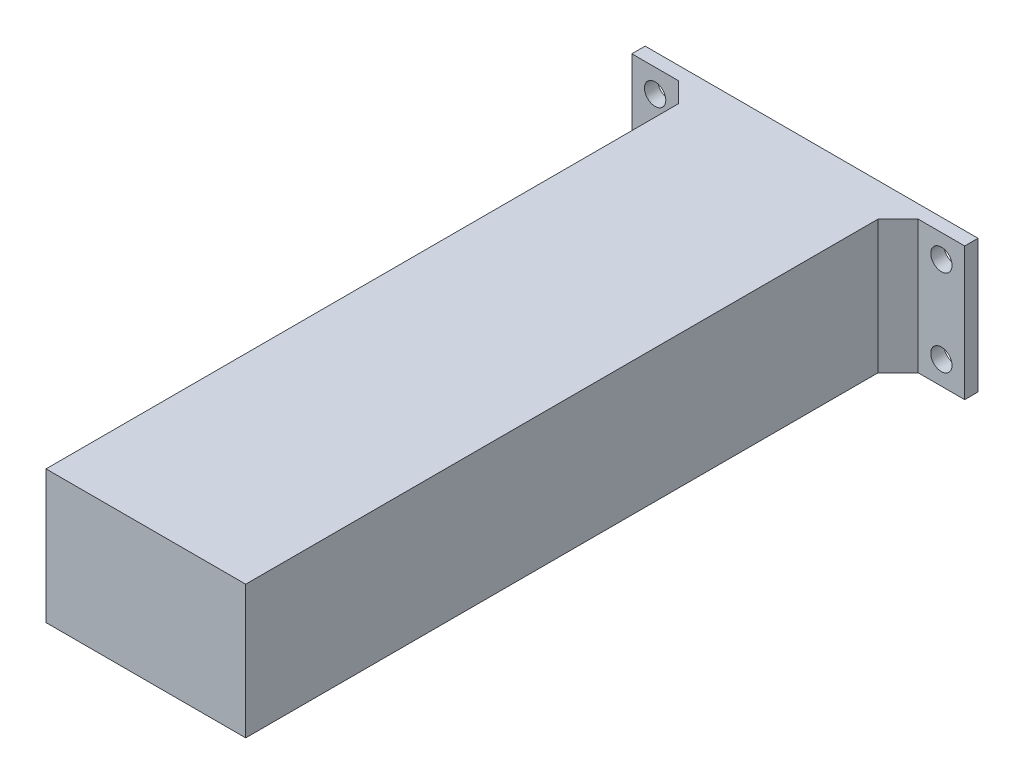
SolidWorks part; units mm, degrees
ref_plane "正面" through (0, 0, 0) normal (0, 0, 1) x (1, 0, 0)
ref_plane "平面" through (0, 0, 0) normal (0, 1, 0) x (1, 0, 0)
ref_plane "右側面" through (0, 0, 0) normal (1, 0, 0) x (0, 0, -1)
sketch "ｽｹｯﾁ1" plane through (0, 0, 0) normal (0, 0, 1) x (1, 0, 0)
  line L1 (-12.7289, 5.1915) -> (17.2711, 5.1915)
  line L2 (-12.7289, 5.1915) -> (-12.7289, -14.8085)
  line L3 (-12.7289, -14.8085) -> (17.2711, -14.8085)
  line L4 (17.2711, 5.1915) -> (17.2711, -14.8085)
  dimension "D1" = 30
  dimension "D2" = 20
extrude "ﾎﾞｽ - 押し出し1" add sketch "ｽｹｯﾁ1" along normal blind 100
sketch "ｽｹｯﾁ3" plane through (17.2711, 0, 0) normal (1, 0, 0) x (0, 0, -1)
  line L0 (-100, -14.8085) -> (0, -14.8085) construction
  line L1 (0, 5.1915) -> (-2, 5.1915)
  line L2 (0, 5.1915) -> (0, -14.8085)
  line L3 (0, -14.8085) -> (-2, -14.8085)
  line L4 (-2, 5.1915) -> (-2, -14.8085)
  dimension "D2" = 2
extrude "ﾎﾞｽ - 押し出し2" add sketch "ｽｹｯﾁ3" along normal blind 10
sketch "ｽｹｯﾁ5" plane through (0, 5.1915, 0) normal (0, 1, 0) x (1, 0, 0)
  line L0 (17.2711, -5) -> (20.2711, -2)
  line L1 (17.2711, -100) -> (17.2711, -2) construction
  line L2 (27.2711, -2) -> (17.2711, -2) construction
  line L3 (20.2711, -2) -> (17.2711, -2)
  line L4 (17.2711, -2) -> (17.2711, -5)
  dimension "D1" = 3
extrude "ﾎﾞｽ - 押し出し3" add sketch "ｽｹｯﾁ5" against normal through all
sketch "ｽｹｯﾁ6" plane through (0, 0, 2) normal (0, 0, 1) x (1, 0, 0)
  line L0 (23.7711, 1.6915) -> (20.2711, 1.6915) construction
  line L1 (20.2711, -14.8085) -> (20.2711, 5.1915) construction
  line L2 (23.7711, 1.6915) -> (27.2711, 1.6915) construction
  line L3 (27.2711, 5.1915) -> (27.2711, -14.8085) construction
  line L4 (23.7711, -11.3085) -> (20.2711, -11.3085) construction
  line L5 (23.7711, -11.3085) -> (27.2711, -11.3085) construction
  line L6 (23.7711, -11.3085) -> (23.7711, -14.8085) construction
  line L7 (27.2711, -14.8085) -> (20.2711, -14.8085) construction
  line L8 (23.7711, 1.6915) -> (23.7711, 5.1915) construction
  line L9 (27.2711, 5.1915) -> (20.2711, 5.1915) construction
  circle A0 centre (23.7711, 1.6915) radius 1.6
  circle A1 centre (23.7711, -11.3085) radius 1.6
  dimension "D1" = 3.2
  dimension "D2" = 3.2
extrude "ｶｯﾄ - 押し出し2" cut sketch "ｽｹｯﾁ6" against normal through all
sketch "ｽｹｯﾁ7" plane through (-12.7289, 0, 0) normal (-1, 0, 0) x (0, 0, 1)
  line L0 (100, 5.1915) -> (0, 5.1915) construction
  line L1 (0, -14.8085) -> (2, -14.8085)
  line L2 (0, -14.8085) -> (0, 5.1915)
  line L3 (0, 5.1915) -> (2, 5.1915)
  line L4 (2, -14.8085) -> (2, 5.1915)
  dimension "D1" = 2
extrude "ﾎﾞｽ - 押し出し4" add sketch "ｽｹｯﾁ7" along normal blind 10
sketch "ｽｹｯﾁ8" plane through (0, -14.8085, 0) normal (0, -1, 0) x (1, 0, 0)
  line L0 (-12.7289, 5) -> (-15.7289, 2)
  line L1 (-12.7289, 100) -> (-12.7289, 2) construction
  line L2 (-22.7289, 2) -> (-12.7289, 2) construction
  line L3 (-15.7289, 2) -> (-12.7289, 2)
  line L4 (-12.7289, 2) -> (-12.7289, 5)
  dimension "D1" = 3
extrude "ﾎﾞｽ - 押し出し5" add sketch "ｽｹｯﾁ8" against normal through all
sketch "ｽｹｯﾁ9" plane through (0, 0, 2) normal (0, 0, 1) x (1, 0, 0)
  line L0 (-19.2289, 1.6915) -> (-15.7289, 1.6915) construction
  line L1 (-15.7289, 5.1915) -> (-15.7289, -14.8085) construction
  line L2 (-19.2289, 1.6915) -> (-22.7289, 1.6915) construction
  line L3 (-22.7289, -14.8085) -> (-22.7289, 5.1915) construction
  line L4 (-19.2289, -11.3085) -> (-22.7289, -11.3085) construction
  line L5 (-19.2289, -11.3085) -> (-15.7289, -11.3085) construction
  line L6 (-19.2289, 1.6915) -> (-19.2289, 5.1915) construction
  line L7 (-22.7289, 5.1915) -> (-15.7289, 5.1915) construction
  line L8 (-19.2289, -11.3085) -> (-19.2289, -14.8085) construction
  line L9 (-22.7289, -14.8085) -> (-15.7289, -14.8085) construction
  circle A0 centre (-19.2289, -11.3085) radius 1.6
  circle A1 centre (-19.2289, 1.6915) radius 1.6
  dimension "D1" = 3.2
  dimension "D2" = 3.2
extrude "ｶｯﾄ - 押し出し3" cut sketch "ｽｹｯﾁ9" against normal through all
